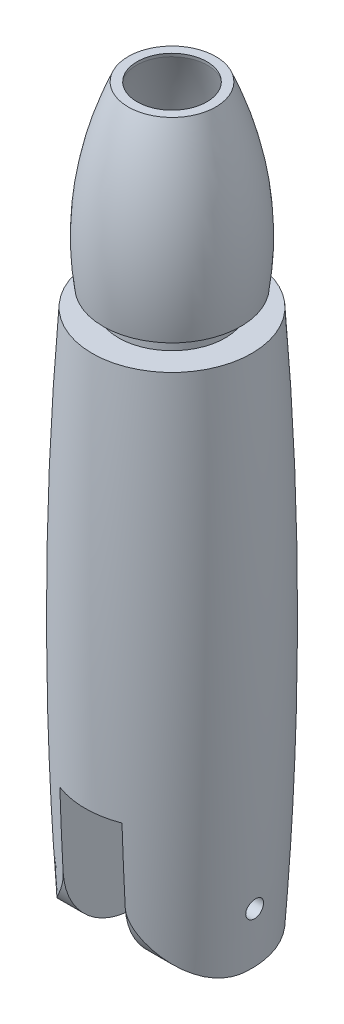
SolidWorks part; units mm, degrees
ref_plane "Front Plane" through (0, 0, 0) normal (0, 0, 1) x (1, 0, 0)
ref_plane "Top Plane" through (0, 0, 0) normal (0, 1, 0) x (1, 0, 0)
ref_plane "Right Plane" through (0, 0, 0) normal (1, 0, 0) x (0, 0, -1)
sketch "Sketch1" plane through (0, 0, 0) normal (0, 0, 1) x (1, 0, 0)
  line L0 (0, 60) -> (3, 60)
  line L3 (9, 26) -> (9, 14)
  line L6 (3, 0) -> (0, 0)
  line L7 (3, 60) -> (9, 60) construction
  line L8 (9, 60) -> (9, 26)
  line L9 (3, 0) -> (9, 0)
  line L10 (9, 0) -> (9, 14)
  line L11 (3, 60) -> (3, 62)
  line L12 (9, 60) -> (9, 82)
  line L13 (3, 62) -> (1.25, 62)
  line L14 (4.07, 82) -> (5.07, 82)
  line L15 (5.07, 82) -> (4.9901, 81.6084)
  line L16 (2.2371, 71.8457) -> (9, 71.8457)
  arc A0 (0, 60) -> (0, 0) centre (449.5, 30) ccw
  spline S0 degree 2 poles (4.07, 82) (-0.1501, 72.0854) (1.25, 62) knots 0 0 0 1 1 1
  spline S1 degree 1 poles (4.9901, 81.6084) (2.2405, 62.1375) knots 0 0 1 1 construction
  spline S2 degree 3 poles (4.9901, 81.6084) (4.6506, 80.8106) (4.0148, 79.1807) (3.1108, 76.3391) (2.4584, 73.4861) (2.0069, 70.2438) (1.8165, 66.613) (2.0156, 63.7572) (2.2405, 62.1375) knots 0 0 0 0 0.125 0.25 0.440447 0.565447 0.75 1 1 1 1 only from (4.9901, 81.6084) to (2.2371, 71.8457)
  point P1 (-1, 30)
  dimension "D1" = 60
  dimension "D2" = 9
  dimension "D3" = 10
  dimension "D4" = 2
  dimension "D5" = 7.75
  dimension "D6" = 4.93
  dimension "D7" = 22
  dimension "D8" = 6
  dimension "D9" = 1
  dimension "D10" = 1
revolve "Revolve1" add sketch "Sketch1" angle 360 about L3 region at (4.2729, 35.5372, 0)
sketch "Sketch2" plane through (0, 0, 0) normal (0, 0, 1) x (1, 0, 0)
  line L7 (5.5, 0) -> (5.5, 16)
  line L14 (5.5, 0) -> (12.5, 0)
  line L17 (0, 0) -> (18, 0)
  line L31 (0, 0) -> (18, 0) construction
  line L32 (5.5, 16) -> (12.5, 16)
  line L33 (12.5, 16) -> (12.5, 0)
  point P9 (9, 0)
  point P11 (9, 0)
  dimension "D4" = 16
  dimension "D5" = 7
extrude "Cut-Extrude1" cut sketch "Sketch2" against normal blind 7.5 and the other way through all contours L33 L32 L7 region at (9, 8, 0)
sketch "Sketch3" plane through (0, 0, 0) normal (1, 0, 0) x (0, 0, -1)
  line L0 (9, 60) -> (-9, 60) construction
  line L5 (-8.2916, 0) -> (9, 0) construction
  line L7 (-8.2916, 0) -> (9, 0)
  circle A0 centre (0, 54) radius 1
  circle A1 centre (0, 6) radius 1
  arc A6 (-8.7686, 7.5712) -> (-0.7801, 0) centre (-0.7801, 8) ccw
  spline S0 degree 3 poles (832.7196, -541.0177) (163.2955, -385.0431) (3.9095, -195.3903) (-8.6003, 4.6244) (-8.6599, 5.6158) (-8.7159, 6.6074) (-8.7524, 7.2685) (-8.7707, 7.6071) (-25.2839, 320.5647) (315.1329, 645.0631) (324.8962, 958.5589) knots -37.460193 -37.460193 -37.460193 -37.460193 0.25 0.25 0.375 0.4375 0.4375 0.5 0.5 58.718393 58.718393 58.718393 58.718393 only from (-8.2916, 0) to (-9.1349, 16) construction
  spline S1 degree 3 poles (-8.2916, 0) (-8.3872, 1.3208) (-8.4764, 2.6419) (-8.6003, 4.6244) (-8.6599, 5.6158) (-8.7159, 6.6074) (-8.7524, 7.2685) (-8.7707, 7.6071) (-8.9301, 10.6276) (-9.0454, 13.3134) (-9.1349, 16) knots 0 0 0 0 0.25 0.25 0.375 0.4375 0.4375 0.5 0.5 1 1 1 1
  dimension "D1" = 2
  dimension "D2" = 6
  dimension "D3" = 8
  dimension "D4" = 6
extrude "Cut-Extrude2" cut sketch "Sketch3" against normal through all both and the other way through all contours A1 | A6 L7 region at (0, 1.675, 6.7468) region at (0, 6, 0)
sketch "Sketch5" plane through (0, 71.8457, 0) normal (0, 1, 0) x (1, 0, 0)
  line L0 (5.5, 4) -> (12.5, 4) construction
  line L3 (12.5, -9.1349) -> (12.5, 7.5) construction
  line L4 (5.5, -9.1349) -> (5.5, 7.5) construction
  circle A0 centre (9, 4) radius 1
  circle A1 centre (9, -3) radius 0.75
  point P12 (9, 4)
  dimension "D1" = 2
  dimension "D2" = 1.5
  dimension "D3" = 4
  dimension "D4" = 3
extrude "Cut-Extrude4" cut sketch "Sketch5" against normal up to next
sketch "Sketch6" plane through (0, 0, -7.5) normal (0, 0, 1) x (1, 0, 0)
  line L1 (5.5, 0) -> (12.5, 0)
  line L2 (5.5, 0) -> (5.5, 6)
  line L3 (5.5, 6) -> (12.5, 6)
  line L4 (12.5, 0) -> (12.5, 6)
  dimension "D1" = 6
extrude "Cut-Extrude5" cut sketch "Sketch6" against normal through all
